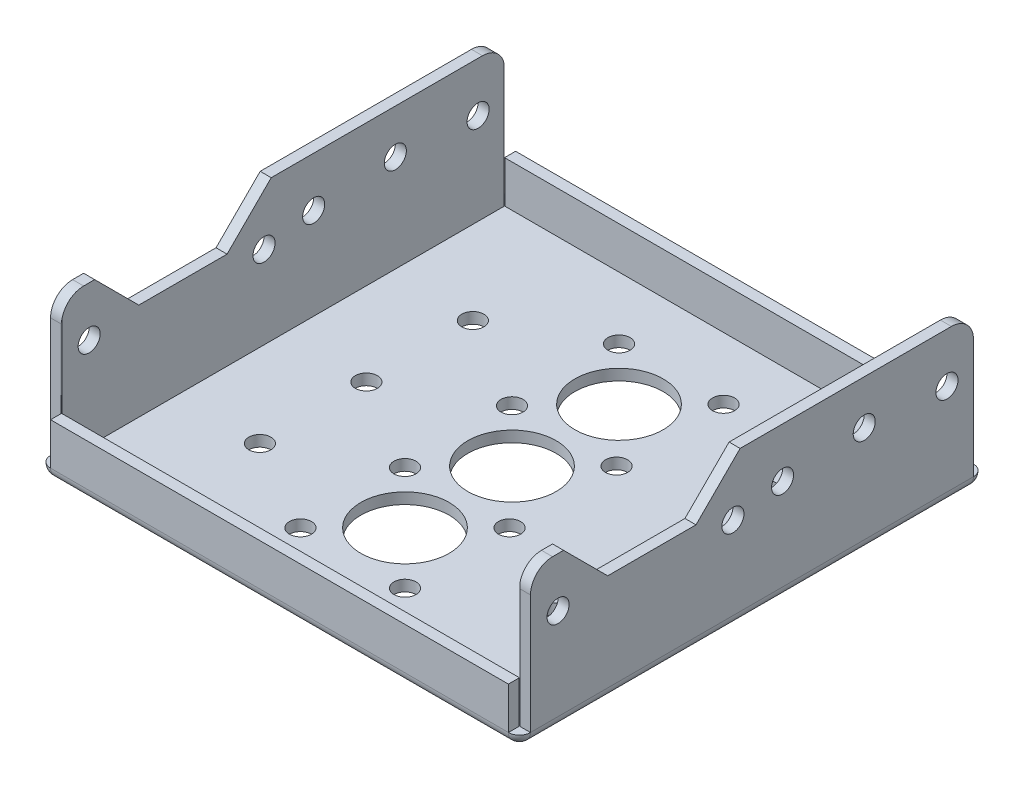
SolidWorks part; units mm, degrees
note: The reader was unsure of these and kept them because the rebuilt part matched: shared geometry of "Sketch2<6>".
ref_plane "Front Plane" through (0, 0, 0) normal (0, 0, 1) x (1, 0, 0)
ref_plane "Top Plane" through (0, 0, 0) normal (0, 1, 0) x (1, 0, 0)
ref_plane "Right Plane" through (0, 0, 0) normal (1, 0, 0) x (0, 0, -1)
sketch "Sketch1" plane through (0, 0, 0) normal (0, 1, 0) x (1, 0, 0)
  line L0 (0, 0) -> (43.5, 0)
  line L1 (43.5, 0) -> (43.5, 42.15)
  line L2 (43.5, 42.15) -> (0, 42.15)
  line L3 (0, 42.15) -> (0, 0)
  line L4 (21.75, 42.15) -> (21.75, 0) construction
  line L5 (0, 21.075) -> (43.5, 21.075) construction
  line L6 (21.75, 21.075) -> (21.75, 30.775) construction
  line L7 (21.75, 21.075) -> (13.4496, 21.075) construction
  line L8 (17.75, 21.075) -> (8.55, 21.075) construction
  line L9 (8.55, 21.075) -> (8.55, 30.725) construction
  line L10 (21.75, 30.775) -> (17.0124, 35.5126) construction
  line L11 (21.75, 21.075) -> (17.0124, 25.8126) construction
  line L12 (21.75, 11.375) -> (17.0124, 16.1126) construction
  line L13 (21.75, 11.375) -> (17.0124, 6.6374) construction
  circle A0 centre (21.75, 21.075) radius 4
  circle A1 centre (21.75, 30.775) radius 4
  circle A2 centre (21.75, 11.375) radius 4
  circle A3 centre (8.55, 21.075) radius 1
  circle A4 centre (8.55, 30.725) radius 1
  circle A5 centre (8.55, 11.425) radius 1
  circle A6 centre (34.95, 11.425) radius 1
  circle A7 centre (34.95, 21.075) radius 1
  circle A8 centre (34.95, 30.725) radius 1
  circle A9 centre (17.0124, 35.5126) radius 1
  circle A10 centre (17.0124, 25.8126) radius 1
  circle A11 centre (17.0124, 16.1126) radius 1
  circle A12 centre (17.0124, 6.6374) radius 1
  circle A13 centre (26.4876, 6.6374) radius 1
  circle A14 centre (26.4876, 16.1126) radius 1
  circle A15 centre (26.4876, 25.8126) radius 1
  circle A16 centre (26.4876, 35.5126) radius 1
  dimension "D1" = 43.5
  dimension "D5" = 8
  dimension "D2" = 42.15
  dimension "D3" = 21.75
  dimension "D4" = 21.075
extrude "Boss-Extrude1" add sketch "Sketch1" along normal blind 1
sketch "Sketch2" plane through (0, 1, 0) normal (0, 1, 0) x (1, 0, 0)
  line L0 (0, 0) -> (1, 0) construction
  line L1 (0, 0) -> (43.5, 0) construction
  line L2 (1, 0) -> (42.5, 0)
  line L3 (42.5, 0) -> (42.5, 0.95)
  line L4 (42.45, 1) -> (1.05, 1)
  line L5 (1, 0.95) -> (1, 0)
  line L6 (0, 21.075) -> (43.5, 21.075) construction
  line L7 (0, 42.15) -> (0, 0) construction
  line L8 (43.5, 0) -> (43.5, 42.15) construction
  line L9 (42.45, 41.15) -> (1.05, 41.15)
  line L10 (42.5, 42.15) -> (42.5, 41.2)
  line L11 (1, 42.15) -> (42.5, 42.15)
  line L12 (1, 41.2) -> (1, 42.15)
  line L13 (0, 41.15) -> (0.95, 41.15)
  line L14 (0.95, 1) -> (0, 1)
  line L15 (0, 1) -> (0, 41.15)
  line L16 (1, 41.1) -> (1, 1.05)
  line L17 (21.75, 42.15) -> (21.75, 0) construction
  line L18 (42.55, 1) -> (43.5, 1)
  line L19 (43.5, 1) -> (43.5, 41.15)
  line L20 (43.5, 41.15) -> (42.55, 41.15)
  line L21 (42.5, 41.1) -> (42.5, 1.05)
  arc A0 (0.95, 41.15) -> (1, 41.1) centre (0.95, 41.1) cw
  arc A1 (1.05, 41.15) -> (1, 41.2) centre (1.05, 41.2) cw
  arc A2 (42.45, 41.15) -> (42.5, 41.2) centre (42.45, 41.2) ccw
  arc A3 (42.5, 41.1) -> (42.55, 41.15) centre (42.55, 41.1) cw
  arc A4 (42.55, 1) -> (42.5, 1.05) centre (42.55, 1.05) cw
  arc A5 (42.5, 0.95) -> (42.45, 1) centre (42.45, 0.95) ccw
  arc A6 (0.95, 1) -> (1, 1.05) centre (0.95, 1.05) ccw
  arc A7 (1.05, 1) -> (1, 0.95) centre (1.05, 0.95) ccw
  point P29 (1, 41.15)
  point P35 (42.5, 41.15)
  point P41 (42.5, 1)
  point P47 (1, 1)
  line M19 (0, 42.15) -> (0, 0)
  line M20 (0, 0) -> (43.5, 0)
  line M22 (43.5, 42.15) -> (0, 42.15)
  dimension "D1" = 0.05
extrude "Boss-Extrude2" add sketch "Sketch2" along normal blind 3.8 contours L12 L9 L10 M22 | L4 L5 L3 M20
extrude "Boss-Extrude5" add sketch "Sketch2<6>" along normal blind 12.8 contours L14 A6 L16 A0 L13 M19 | L19 L20 A3 L21 A4 L18
sketch "Sketch2<6>" plane through (0, 1, 0) normal (0, 1, 0) x (1, 0, 0) same geometry as "Sketch2"
fillet "Fillet1" radius 1 4 edges at (21.75, 0, -42.15) (43.5, 0, -21.075) (0, 0, -21.075) (21.75, 0, 0)
sketch "Sketch3" plane through (0, 0, 0) normal (-1, 0, 0) x (0, 0, 1)
  line L0 (-41.15, 13.8) -> (-41.15, 9.3) construction
  line L1 (-41.15, 9.3) -> (-1, 9.3) construction
  line L2 (-41.15, 9.3) -> (-38.75, 9.3) construction
  line L3 (-41.15, 13.8) -> (-31.25, 13.8) construction
  line L4 (-41.15, 13.8) -> (-41.15, 1)
  line L5 (-41.15, 1) -> (-1, 1)
  line L6 (-1, 1) -> (-1, 13.8)
  line L7 (-1, 13.8) -> (-41.15, 13.8)
  line L8 (-41.15, 11.8) -> (-41.15, 1)
  line L9 (-41.15, 1) -> (-1, 1)
  line L10 (-1, 1) -> (-1, 11.8)
  line L11 (-3, 13.8) -> (-39.15, 13.8)
  line L12 (-31.25, 13.8) -> (-31.25, 9.8) construction
  line L13 (-37.75, 9.3) -> (-23.85, 9.3) construction
  line L14 (-23.85, 9.3) -> (-19.35, 9.3) construction
  line L15 (-19.35, 9.3) -> (-19.35, 1) construction
  line L16 (-19.35, 1) -> (-19.35, 8.5) construction
  line L17 (-1, 9.3) -> (-3.5, 9.3) construction
  line L18 (-1, 13.8) -> (-4, 13.8) construction
  line L19 (-4, 13.8) -> (-4, 9.8) construction
  line L20 (-4, 9.8) -> (-20, 9.8) construction
  line L21 (-20, 9.8) -> (-20, 13.8) construction
  line L22 (-20, 9.8) -> (-16, 9.8) construction
  line L23 (-4, 9.8) -> (-8, 9.8) construction
  line L24 (-8, 9.8) -> (-4, 13.8)
  line L25 (-20, 13.8) -> (-16, 9.8)
  line L26 (-16, 9.8) -> (-8, 9.8)
  arc A0 (-1, 11.8) -> (-3, 13.8) centre (-3, 11.8) ccw
  arc A1 (-41.15, 11.8) -> (-39.15, 13.8) centre (-39.15, 11.8) cw
  circle A2 centre (-38.75, 9.3) radius 1
  circle A3 centre (-31.25, 9.8) radius 1
  circle A4 centre (-23.85, 9.3) radius 1
  circle A5 centre (-19.35, 8.5) radius 1
  circle A6 centre (-3.5, 9.3) radius 1
  line M9 (-41.15, 13.8) -> (-41.15, 1)
  line M11 (-1, 1) -> (-1, 13.8)
  line M12 (-1, 13.8) -> (-41.15, 13.8)
  dimension "D2" = 2
  dimension "D3" = 9.9
  dimension "D1" = 0
extrude "Cut-Extrude1" cut sketch "Sketch3" against normal through all contours A0 M11 M12 | L25 L26 L24 L11 | A5 | A4 | A3 | A2 | A1 M9 M12 | A6
